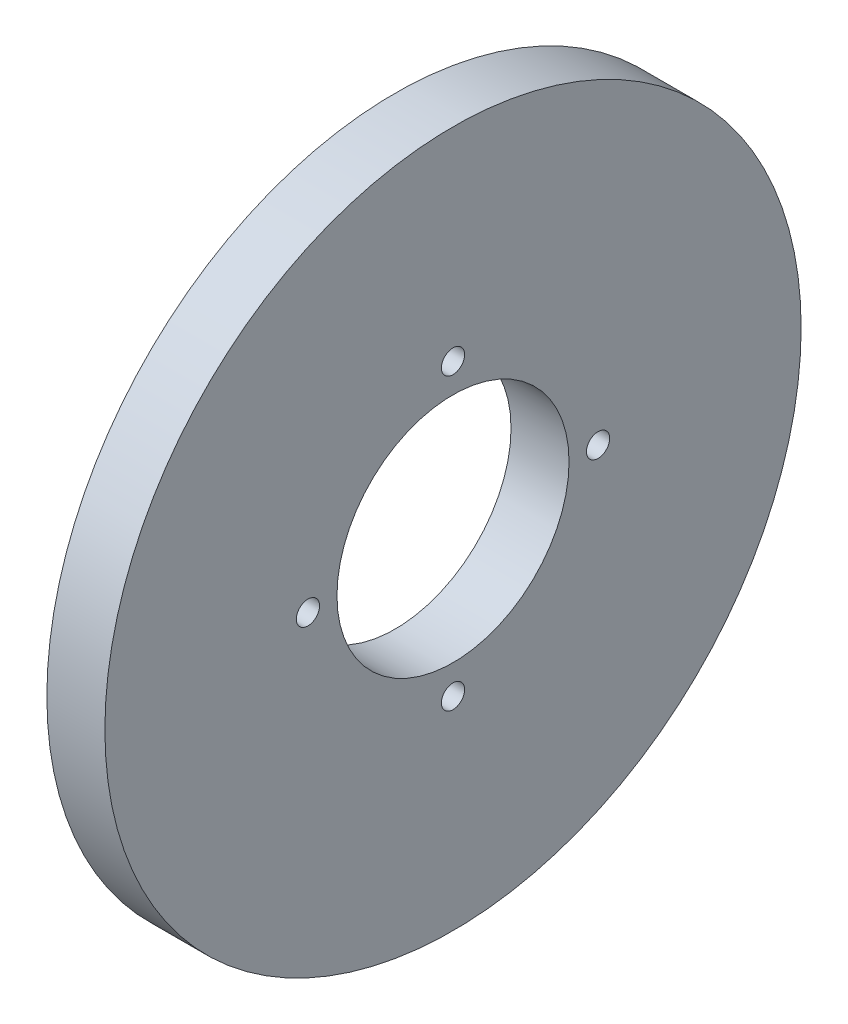
SolidWorks part; units mm, degrees
ref_plane "Front Plane" through (0, 0, 0) normal (0, 0, 1) x (1, 0, 0)
ref_plane "Top Plane" through (0, 0, 0) normal (0, 1, 0) x (1, 0, 0)
ref_plane "Right Plane" through (0, 0, 0) normal (1, 0, 0) x (0, 0, -1)
sketch "Sketch1" plane through (0, 0, 0) normal (1, 0, 0) x (0, 0, -1)
  circle A0 centre (0, 0) radius 20
  circle A1 centre (0, 0) radius 60
  dimension "D1" = 120
  dimension "D2" = 40
extrude "Boss-Extrude1" add sketch "Sketch1" along normal mid plane 10
sketch "Sketch2" plane through (5, 0, 0) normal (1, 0, 0) x (0, 0, -1)
  circle A0 centre (0, 0) radius 25 construction
  circle A1 centre (0, 25) radius 2
  circle A2 centre (25, 0) radius 2
  circle A3 centre (0, -25) radius 2
  circle A4 centre (-25, 0) radius 2
  point P14 (0, 0)
  dimension "D1" = 50
  dimension "D2" = 4
  dimension "D4" = 25
  dimension "D5" = 25
  dimension "D3" = 4
extrude "Cut-Extrude1" cut sketch "Sketch2" against normal through all
